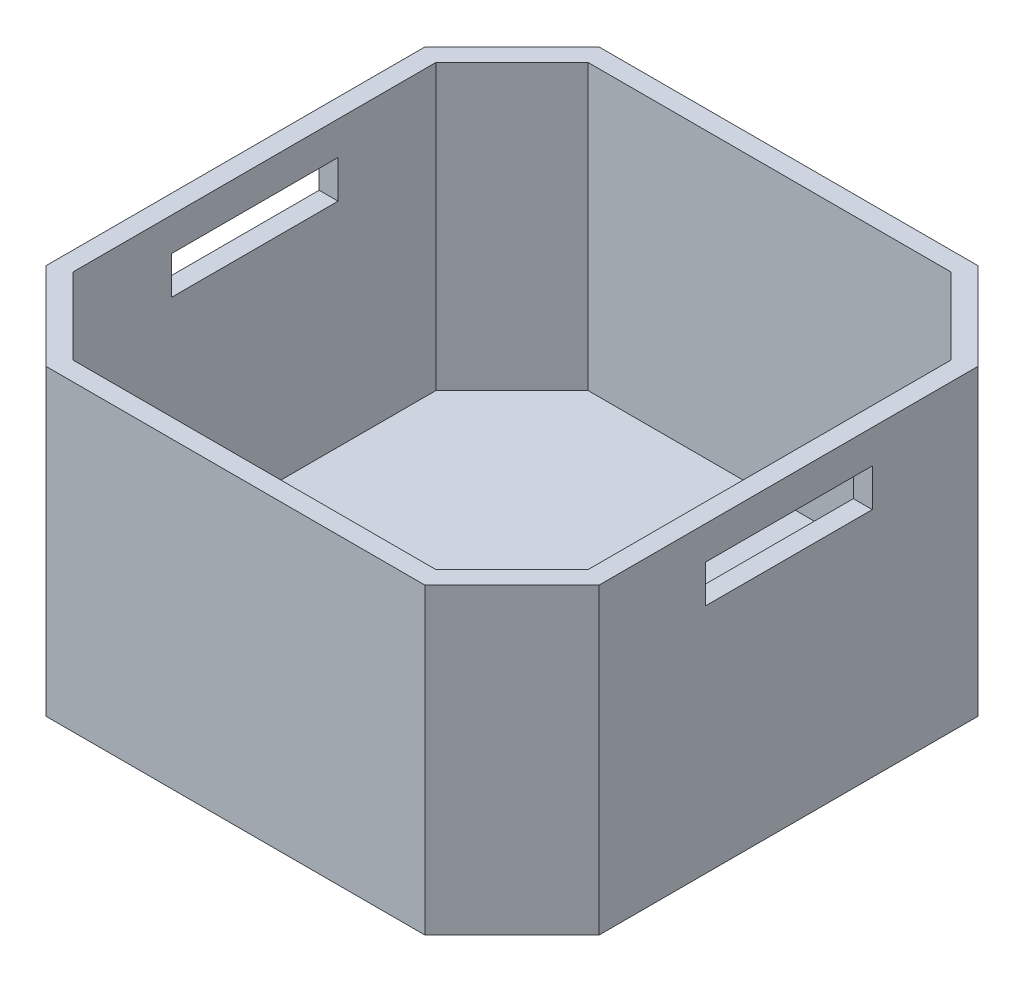
SolidWorks part; units mm, degrees
ref_plane "Alzado" through (0, 0, 0) normal (0, 0, 1) x (1, 0, 0)
ref_plane "Planta" through (0, 0, 0) normal (0, 1, 0) x (1, 0, 0)
ref_plane "Vista lateral" through (0, 0, 0) normal (1, 0, 0) x (0, 0, -1)
sketch "Croquis3" plane through (0, 0, 0) normal (0, 1, 0) x (1, 0, 0)
  line L0 (-25, -32.5) -> (25, -32.5) construction
  line L1 (-25, 32.5) -> (25, 32.5) construction
  line L2 (-25, -32.5) -> (25, 32.5) construction
  line L3 (-25, 32.5) -> (25, -32.5) construction
  line L4 (32.5, 25) -> (32.5, -25) construction
  line L5 (25, -32.5) -> (32.5, -25) construction
  line L6 (32.5, 25) -> (25, 32.5) construction
  line L7 (-32.5, 25) -> (-32.5, -25) construction
  line L8 (-32.5, -25) -> (-25, -32.5) construction
  line L9 (-32.5, 25) -> (-25, 32.5) construction
  line L10 (-25, -32.5) -> (-25, -36.5) construction
  line L11 (-32.5, -25) -> (-36.5, -25) construction
  line L12 (-32.5, 25) -> (-36.5, 25) construction
  line L13 (-25, 32.5) -> (-25, 36.5)
  line L14 (25, 32.5) -> (25, 36.5) construction
  line L15 (32.5, 25) -> (36.5, 25) construction
  line L16 (32.5, -25) -> (36.5, -25) construction
  line L17 (25, -32.5) -> (25, -36.5) construction
  line L18 (-25, -36.5) -> (25, -36.5)
  line L19 (36.5, -25) -> (36.5, 25)
  line L20 (25, 36.5) -> (-25, 36.5)
  line L21 (-36.5, 25) -> (-36.5, -25)
  line L22 (-36.5, -25) -> (-25, -36.5)
  line L23 (-36.5, 25) -> (-25, 36.5)
  line L24 (25, 36.5) -> (36.5, 25)
  line L25 (25, -36.5) -> (36.5, -25)
  point P0 (0, 0)
  point P5 (0, 32.5)
  dimension "D1" = 65
  dimension "D2" = 50
  dimension "D3" = 50
  dimension "D4" = 25
  dimension "D5" = 25
  dimension "D6" = 4
  dimension "D8" = 4
  dimension "D10" = 4
extrude "Saliente-Extruir1" add sketch "Croquis3" along normal blind 40 contours L18 L25 L19 L24 L20 L1 L6 L4 L5 L0 L8 L7 L9 L23 L21 L22 region at (0, 0, 0)
shell "Vaciado1" thickness 2.5 removed face at (0, 40, 0)
sketch "Croquis5" plane through (-36.5, 0, 0) normal (-1, 0, 0) x (0, 0, 1)
  line L0 (-25, 40) -> (-25, 0) construction
  line L1 (-11.05, 35.6) -> (10.95, 35.6)
  line L2 (-11.05, 35.6) -> (-11.05, 30.6)
  line L3 (-11.05, 30.6) -> (10.95, 30.6)
  line L4 (10.95, 35.6) -> (10.95, 30.6)
  dimension "D1" = 22
  dimension "D2" = 13.95
  dimension "D3" = 4.4
  dimension "D4" = 5
extrude "Cortar-Extruir1" cut sketch "Croquis5" against normal through all
